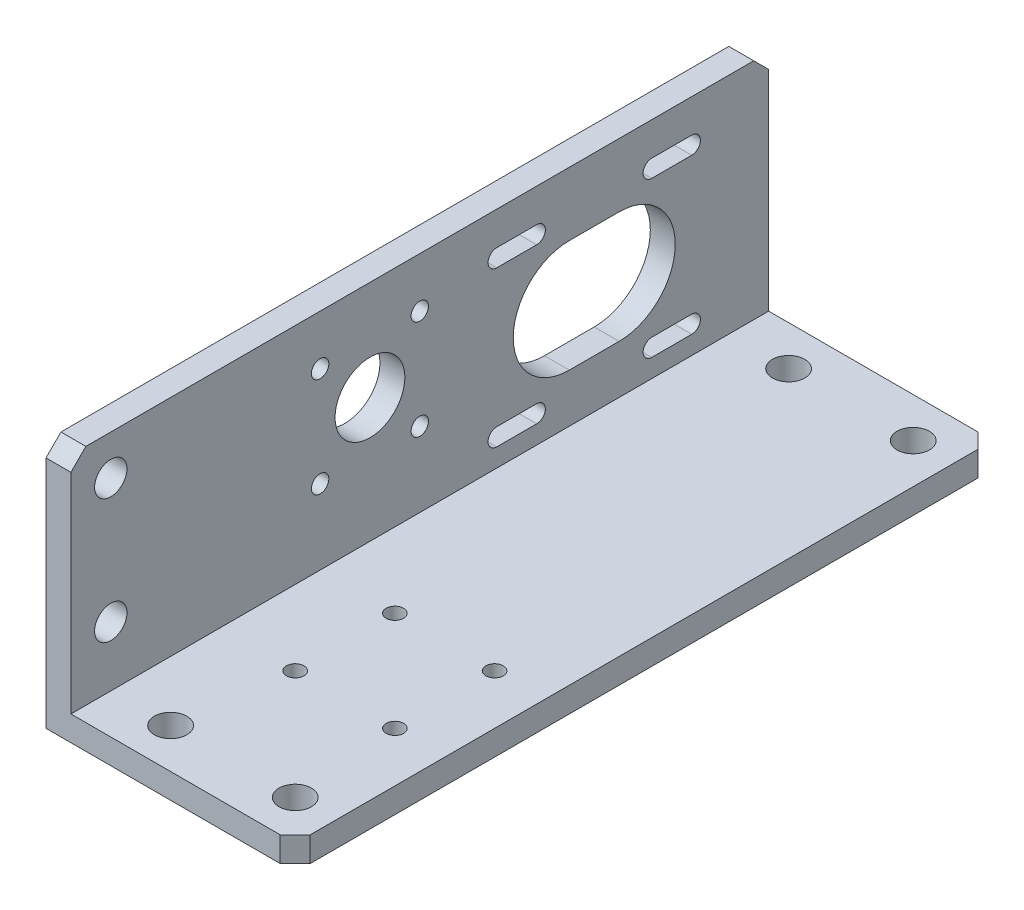
SolidWorks part; units mm, degrees
material "Lega 1060"
ref_plane "Piano frontale" through (0, 0, 0) normal (0, 0, 1) x (1, 0, 0)
ref_plane "Piano superiore" through (0, 0, 0) normal (0, 1, 0) x (1, 0, 0)
ref_plane "Piano destro" through (0, 0, 0) normal (1, 0, 0) x (0, 0, -1)
sketch "Schizzo1" plane through (0, 0, 0) normal (0, 0, 1) x (1, 0, 0)
  line L0 (0, 0) -> (0, 50)
  line L1 (0, 50) -> (5, 50)
  line L2 (5, 50) -> (5, 5)
  line L3 (5, 5) -> (50, 5)
  line L4 (50, 5) -> (50, 0)
  line L5 (50, 0) -> (0, 0)
  dimension "D1" = 5
  dimension "D2" = 5
  dimension "D3" = 50
  dimension "D4" = 50
extrude "Estrusione-Estrusione1" add sketch "Schizzo1" along normal blind 140
sketch "Schizzo2" plane through (0, 0, 0) normal (0, -1, 0) x (1, 0, 0)
  line L0 (5.4524, 132) -> (42.7933, 132) construction
  line L1 (0, 140) -> (50, 140) construction
  line L5 (50, 140) -> (50, 0) construction
  point P4 (17, 132)
  point P5 (42, 132)
  dimension "D1" = 8
  dimension "D2" = 25
  dimension "D3" = 8
sketch "Schizzo3" plane through (0, 0, 0) normal (-1, 0, 0) x (0, 0, 1)
  line L0 (132, 44.621) -> (132, 5.772) construction
  line L1 (140, 50) -> (140, 0) construction
  line L2 (140, 50) -> (0, 50) construction
  point P4 (132, 42)
  point P5 (132, 17)
  dimension "D1" = 8
  dimension "D2" = 8
  dimension "D3" = 25
hole_wizard "Foro Ø6.5 (6.5)-1" positions "Schizzo5" profile "Schizzo4" hole size "Ø6.5" standard "ISO" end condition through all
sketch "Schizzo5" plane through (0, 0, 0) normal (0, -1, 0) x (-1, 0, 0)
  point P0 (-17, -132)
  point P3 (-42, -132)
sketch "Schizzo4" plane through (17, 0, 132) normal (1, 0, 0) x (0, 0, -1)
  line L0 (0, 0) -> (0, 50)
  line L1 (0, 50) -> (3.25, 50)
  line L2 (3.25, 50) -> (3.25, 0)
  line L5 (3.25, 0) -> (0, 0)
  line L11 (0, -6.35) -> (0, 107.95) construction
  dimension "Thru Hole Dia." = 6.5
  dimension "Thru Hole Depth" = 50
hole_wizard "Foro Ø6.5 (6.5)-2" positions "Schizzo7" profile "Schizzo6" hole size "Ø6.5" standard "ISO"
sketch "Schizzo7" plane through (0, 0, 0) normal (-1, 0, 0) x (0, 0, 1)
  point P1 (132, 42)
  point P4 (132, 17)
sketch "Schizzo6" plane through (0, 42, 132) normal (0, 1, 0) x (0, 0, 1)
  line L0 (0, 0) -> (0, 6.9528)
  line L1 (0, 6.9528) -> (3.25, 5)
  line L2 (3.25, 5) -> (3.25, 0)
  line L5 (3.25, 0) -> (0, 0)
  line L10 (0, 6.9528) -> (-3.25, 5) construction
  line L11 (0, -6.35) -> (0, 107.95) construction
  dimension "Hole Dia." = 6.5
  dimension "Hole Depth" = 5
  dimension "Drill Angle" = 118
ref_plane "Piano1" through (0, 0, 70) normal (0, 0, 1) x (1, 0, 0)
mirror "Specchia1" about plane through (0, 0, 70) normal (0, 0, 1) of "Foro Ø6.5 (6.5)-1"
sketch "Schizzo10" plane through (0, 0, 0) normal (-1, 0, 0) x (0, 0, 1)
  line L0 (20.1125, 30) -> (43.2424, 30) construction
  line L1 (80, 42.2663) -> (80, 14.8621) construction
  line L2 (49.1906, 60.8094) -> (80, 30) construction
  line L3 (140, 50) -> (140, 0) construction
  line L5 (140, 50) -> (0, 50) construction
  circle A0 centre (70, 40) radius 1.75
  circle A1 centre (90, 40) radius 1.75
  circle A3 centre (90, 20) radius 1.75
  circle A4 centre (70, 20) radius 1.75
  circle A5 centre (80, 30) radius 7
  point P8 (80, 30)
  point P20 (80, 30)
  dimension "D1" = 3.5
  dimension "D7" = 14
  dimension "D2" = 20
  dimension "D3" = 45
  dimension "D5" = 60
  dimension "D6" = 20
  dimension "D4" = 4
extrude "Taglio-Estrusione3" cut sketch "Schizzo10" against normal up to next
sketch "Schizzo11" plane through (0, 0, 0) normal (0, -1, 0) x (1, 0, 0)
  line L0 (30, 100) -> (14.4837, 100) construction
  line L1 (30, 100) -> (4.5929, 74.5929) construction
  line L3 (50, 140) -> (50, 0) construction
  line L4 (0, 140) -> (50, 140) construction
  circle A0 centre (20, 90) radius 1.75
  circle A3 centre (20, 110) radius 1.75
  circle A4 centre (40, 110) radius 1.75
  circle A5 centre (40, 90) radius 1.75
  point P2 (30, 100)
  point P17 (30, 100)
  dimension "D2" = 3.5
  dimension "D1" = 20
  dimension "D3" = 45
  dimension "D5" = 20
  dimension "D6" = 40
  dimension "D4" = 4
extrude "Taglio-Estrusione4" cut sketch "Schizzo11" against normal up to next
sketch "Schizzo13" plane through (0, 0, 0) normal (-1, 0, 0) x (0, 0, 1)
  line L0 (60.9365, 26) -> (8.6526, 26) construction
  line L2 (140, 0) -> (0, 0) construction
  line L3 (15.4437, 41.5563) -> (23.4437, 41.5563) construction
  line L4 (15.4437, 43.3063) -> (23.4437, 43.3063)
  line L5 (15.4437, 39.8063) -> (23.4437, 39.8063)
  line L6 (15.4437, 10.4437) -> (23.4437, 10.4437) construction
  line L7 (15.4437, 8.6937) -> (23.4437, 8.6937)
  line L8 (15.4437, 12.1937) -> (23.4437, 12.1937)
  line L9 (35, 26) -> (35, 7.2619) construction
  line L10 (54.5563, 41.5563) -> (46.5563, 41.5563) construction
  line L11 (54.5563, 43.3063) -> (46.5563, 43.3063)
  line L12 (54.5563, 39.8063) -> (46.5563, 39.8063)
  line L13 (54.5563, 10.4437) -> (46.5563, 10.4437) construction
  line L14 (54.5563, 8.6937) -> (46.5563, 8.6937)
  line L15 (54.5563, 12.1937) -> (46.5563, 12.1937)
  line L16 (40, 26) -> (30, 26) construction
  line L17 (40, 14.75) -> (30, 14.75)
  line L18 (40, 37.25) -> (30, 37.25)
  arc A0 (54.5563, 43.3063) -> (54.5563, 39.8063) centre (54.5563, 41.5563) cw
  circle A1 centre (80, 30) radius 7 construction
  arc A2 (15.4437, 43.3063) -> (15.4437, 39.8063) centre (15.4437, 41.5563) ccw
  arc A3 (46.5563, 39.8063) -> (46.5563, 43.3063) centre (46.5563, 41.5563) cw
  arc A4 (15.4437, 8.6937) -> (15.4437, 12.1937) centre (15.4437, 10.4437) cw
  arc A5 (23.4437, 12.1937) -> (23.4437, 8.6937) centre (23.4437, 10.4437) cw
  arc A7 (23.4437, 39.8063) -> (23.4437, 43.3063) centre (23.4437, 41.5563) ccw
  arc A10 (54.5563, 8.6937) -> (54.5563, 12.1937) centre (54.5563, 10.4437) ccw
  arc A11 (46.5563, 12.1937) -> (46.5563, 8.6937) centre (46.5563, 10.4437) ccw
  arc A12 (40, 14.75) -> (40, 37.25) centre (40, 26) ccw
  arc A13 (30, 37.25) -> (30, 14.75) centre (30, 26) ccw
  point P8 (35, 26)
  point P13 (50.5563, 41.5563)
  point P17 (19.4437, 10.4437)
  point P19 (35, 26)
  point P22 (19.4437, 41.5563)
  point P40 (50.5563, 10.4437)
  point P47 (35, 26)
  dimension "D2" = 22.5
  dimension "D3" = 10
  dimension "D5" = 26
  dimension "D6" = 45
  dimension "D8" = 3.5
  dimension "D9" = 8
extrude "Taglio-Estrusione6" cut sketch "Schizzo13" against normal up to next
chamfer "Smusso1" distance 3 angle 45 4 edges at (50, 2.5, 0) (2.5, 50, 0) (50, 2.5, 140) (2.5, 50, 140)
